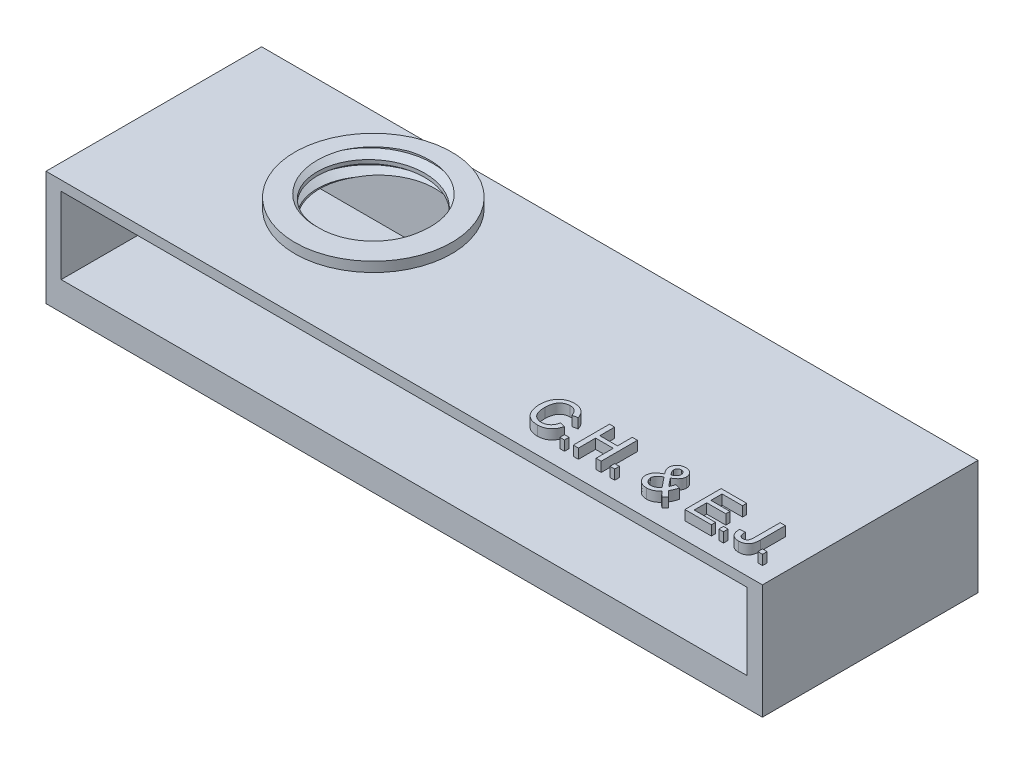
SolidWorks part; units mm, degrees
ref_plane "Ebene vorne" through (0, 0, 0) normal (0, 0, 1) x (1, 0, 0)
ref_plane "Ebene oben" through (0, 0, 0) normal (0, 1, 0) x (1, 0, 0)
ref_plane "Ebene rechts" through (0, 0, 0) normal (1, 0, 0) x (0, 0, -1)
sketch "Skizze1" plane through (0, 0, 0) normal (0, 1, 0) x (1, 0, 0)
  line L1 (-46.4165, 18.2033) -> (26.6835, 18.2033)
  line L2 (-46.4165, 18.2033) -> (-46.4165, -3.7967)
  line L3 (-46.4165, -3.7967) -> (26.6835, -3.7967)
  line L4 (26.6835, 18.2033) -> (26.6835, -3.7967)
  dimension "D1" = 73.1
  dimension "D2" = 22
extrude "Basis" add sketch "Skizze1" along normal blind 11.7
ref_plane "Ebene seitlich Handyschlitz" through (0, 0, 3.7967) normal (0, 0, 1) x (1, 0, 0)
sketch "Skizze2" plane through (0, 0, 3.7967) normal (0, 0, 1) x (1, 0, 0)
  line L1 (-44.8665, 10.7) -> (25.1335, 10.7)
  line L2 (-44.8665, 10.7) -> (-44.8665, 2.9)
  line L3 (-44.8665, 2.9) -> (25.1335, 2.9)
  line L4 (25.1335, 10.7) -> (25.1335, 2.9)
  line L5 (-46.4165, 11.7) -> (-46.4165, 0) construction
  line L6 (-46.4165, 11.7) -> (26.6835, 11.7) construction
  dimension "D1" = 70
  dimension "D2" = 7.8
  dimension "D3" = 1
  dimension "D4" = 1.55
extrude "Handyschlitz" cut sketch "Skizze2" against normal blind 21.25
ref_plane "Ebene oben auf Basis für Zylinder" through (0, 11.7, 0) normal (0, 1, 0) x (1, 0, 0)
sketch "Skizze3" plane through (0, 11.7, 0) normal (0, 1, 0) x (1, 0, 0)
  line L0 (-46.4165, 18.2033) -> (-46.4165, -3.7967) construction
  line L1 (26.6835, 18.2033) -> (-46.4165, 18.2033) construction
  circle A0 centre (-26.4165, 9.6033) radius 6.3
  dimension "D1" = 20
  dimension "D2" = 8.6
extrude "Zylinder" add sketch "Skizze3" along normal blind 1
ref_plane "Ebene oben auf Zylinder" through (0, 12.7, 0) normal (0, 1, 0) x (1, 0, 0)
sketch "Skizze6" plane through (0, 11.7, 0) normal (0, 1, 0) x (1, 0, 0)
  circle A0 centre (-26.4165, 9.6033) radius 8
extrude "Aufsatz-Linear austragen1" add sketch "Skizze6" along normal blind 1 contours A0
sketch "Skizze8" plane through (0, 12.7, 0) normal (0, 1, 0) x (1, 0, 0)
  circle A0 centre (-26.4165, 9.6033) radius 6.3
extrude "Schnitt-Linear austragen2" cut sketch "Skizze8" against normal blind 6
ref_plane "Ebene3" through (0, 10.7, 0) normal (0, -1, 0) x (-1, 0, 0)
sketch "Skizze12" plane through (0, 12.7, 0) normal (0, 1, 0) x (1, 0, 0)
  circle A0 centre (-26.4165, 9.6033) radius 7.5
thread "Gewinde2" pitch 1.5 method extrude profile "Gewindeprofil2" start angle 0, offset 1.6, length 8, pitch 1.5, diameter 12.6
ref_plane "Ebene5" through (-32.7165, 14.3, -9.6033) normal (0, 0, 1) x (-1, 0, 0)
sketch "Gewindeprofil2" plane through (-32.7165, 14.3, -9.6033) normal (0, 0, 1) x (-1, 0, 0)
  line L0 (0, 0) -> (0, 1.5) construction
  line L11 (0, 0) -> (0, 1.3125)
  line L12 (0, 1.3125) -> (-0.8119, 0.8437)
  line L13 (-0.8119, 0.8437) -> (-0.8119, 0.4687)
  line L15 (-0.8119, 0.4687) -> (0, 0)
  line L17 (-0.8119, 0.6562) -> (0, 0.6562) construction
  point P2 (0, 0)
  dimension "Pitch" = 1.5
  dimension "Profile_Angle" = 60
  dimension "Profile_Land" = 0.375
  dimension "Profile_Height" = 0.8119
extrude "Schnitt-Linear austragen5" cut sketch "Skizze12" along normal blind 6 contours A0
sketch "Skizze17" plane through (0, 10.7, 0) normal (0, -1, 0) x (-1, 0, 0)
  line L1 (13.3814, 0) -> (43.6823, 0)
  line L2 (13.3814, 0) -> (13.3814, 16.2694)
  line L3 (13.3814, 16.2694) -> (43.6823, 16.2694)
  line L4 (43.6823, 0) -> (43.6823, 16.2694)
extrude "Schnitt-Linear austragen7" cut sketch "Skizze17" along normal blind 6
ref_plane "Ebene für Logo" through (0, 0, 0) normal (0, -1, 0) x (-1, 0, 0)
sketch "Skizze24" plane through (0, 0, 0) normal (0, -1, 0) x (-1, 0, 0)
  line L1 (33.7615, 1.4341) -> (32.0294, -1.5659)
  line L2 (32.0294, -1.5659) -> (35.4935, -1.5659)
  line L3 (35.4935, -1.5659) -> (33.7615, 1.4341)
  line L4 (35.9478, -1.5381) -> (37.6798, 1.4619)
  line L5 (37.6798, 1.4619) -> (34.2157, 1.4619)
  line L6 (34.2157, 1.4619) -> (35.9478, -1.5381)
  line L7 (38.0931, 1.4341) -> (36.3611, -1.5659)
  line L8 (36.3611, -1.5659) -> (39.8252, -1.5659)
  line L9 (39.8252, -1.5659) -> (38.0931, 1.4341)
  line L10 (40.2382, -1.5381) -> (41.9702, 1.4619)
  line L11 (41.9702, 1.4619) -> (38.5061, 1.4619)
  line L12 (38.5061, 1.4619) -> (40.2382, -1.5381)
  line L13 (42.3422, 1.4341) -> (40.6101, -1.5659)
  line L14 (40.6101, -1.5659) -> (44.0742, -1.5659)
  line L15 (44.0742, -1.5659) -> (42.3422, 1.4341)
  line L16 (35.9475, 4.8546) -> (34.2154, 1.8546)
  line L17 (34.2154, 1.8546) -> (37.6795, 1.8546)
  line L18 (37.6795, 1.8546) -> (35.9475, 4.8546)
  line L19 (38.1338, 1.9341) -> (39.8658, 4.9341)
  line L20 (39.8658, 4.9341) -> (36.4017, 4.9341)
  line L21 (36.4017, 4.9341) -> (38.1338, 1.9341)
  line L22 (40.2791, 4.8546) -> (38.547, 1.8546)
  line L23 (38.547, 1.8546) -> (42.0111, 1.8546)
  line L24 (42.0111, 1.8546) -> (40.2791, 4.8546)
  line L28 (38.1338, 8.3316) -> (36.4017, 5.3316)
  line L29 (36.4017, 5.3316) -> (39.8658, 5.3316)
  line L30 (39.8658, 5.3316) -> (38.1338, 8.3316)
  circle A0 centre (33.7615, -0.5659) radius 1 construction
  circle A1 centre (35.9478, 0.4619) radius 1 construction
  circle A2 centre (38.0931, -0.5659) radius 1 construction
  circle A3 centre (40.2382, 0.4619) radius 1 construction
  circle A4 centre (42.3422, -0.5659) radius 1 construction
  circle A5 centre (35.9475, 2.8546) radius 1 construction
  circle A6 centre (38.1338, 3.9341) radius 1 construction
  circle A7 centre (40.2791, 2.8546) radius 1 construction
  circle A8 centre (38.1338, 6.3316) radius 1 construction
sketch "Skizze25" plane through (0, 0, 0) normal (0, -1, 0) x (-1, 0, 0)
  text T0 "EAH JENA         " font "Arial" height 3.5
extrude "EAH Jena" add sketch "Skizze25" along normal blind 1
extrude "LOGO" add sketch "Skizze24" along normal blind 1
ref_plane "Ebene für Schrift oben" through (0, 11.7, 0) normal (0, 1, 0) x (1, 0, 0)
sketch "Skizze26" plane through (0, 11.7, 0) normal (0, 1, 0) x (1, 0, 0)
  text T0 "C.H. & E.J." font "Arial" height 3.7
extrude "C.H. & E.J." add sketch "Skizze26" along normal blind 1
